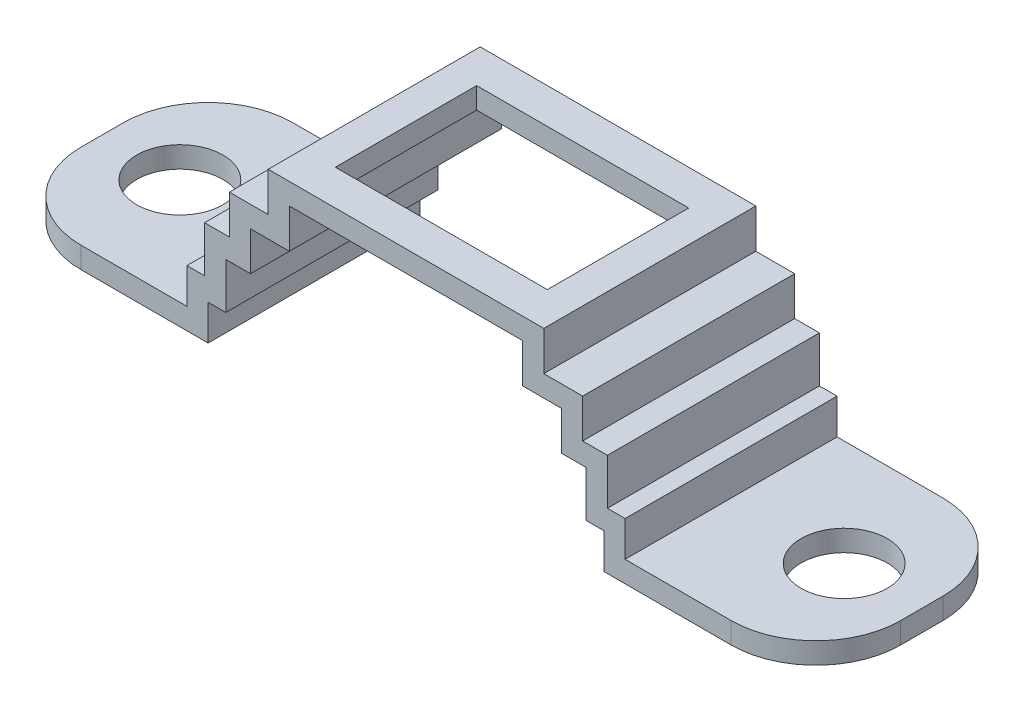
SolidWorks part; units mm, degrees
material "PBT General Purpose"
ref_plane "Front Plane" through (0, 0, 0) normal (0, 0, 1) x (1, 0, 0)
ref_plane "Top Plane" through (0, 0, 0) normal (0, 1, 0) x (1, 0, 0)
ref_plane "Right Plane" through (0, 0, 0) normal (1, 0, 0) x (0, 0, -1)
sketch "Sketch1" plane through (0, 0, 0) normal (0, 0, 1) x (1, 0, 0)
  line L0 (-58, 4.5) -> (-28, 4.5)
  line L1 (-28, 4.5) -> (-28, 9.5)
  line L2 (-28, 9.5) -> (-25.5, 9.5)
  line L3 (-25.5, 9.5) -> (-25.5, 16)
  line L4 (-25.5, 16) -> (-22, 16)
  line L5 (-22, 16) -> (-22, 21.5)
  line L6 (-22, 21.5) -> (-16.5, 21.5)
  line L7 (-16.5, 21.5) -> (-16.5, 27.05)
  line L8 (-16.5, 27.05) -> (0, 27.05)
  circle A0 centre (0, 0) radius 27.05
  dimension "D1" = 54.1
  dimension "D2" = 30
  dimension "D3" = 4.5
  dimension "D4" = 28
  dimension "D5" = 5
  dimension "D6" = 2.5
  dimension "D7" = 6.5
  dimension "D8" = 3.5
  dimension "D9" = 5.5
  dimension "D10" = 5.5
  dimension "D11" = 16.5
  dimension "D12" = 5.55
extrude "Extrude-Thin1" add sketch "Sketch1" along normal mid plane 30 thin contours L0 L1 L2 L3 L4 L5 L6 L7 L8 thin type one direction reverse wall 3
sketch "Sketch2" plane through (0, 7.5, 0) normal (0, 1, 0) x (1, 0, 0)
  line L0 (0, -15) -> (0, 15) construction
  circle A0 centre (-47, 0) radius 6.1
  dimension "D1" = 12.2
  dimension "D2" = 47
extrude "Cut-Extrude1" cut sketch "Sketch2" against normal through all
fillet "Fillet1" radius 12 2 edges at (-58, 6, -15) (-58, 6, 15)
mirror "Mirror1" about plane through (0, 30.05, 15) normal (1, 0, 0) of "Fillet1", "Cut-Extrude1", "Extrude-Thin1"
sketch "Sketch3" plane through (0, 30.05, 0) normal (0, 1, 0) x (1, 0, 0)
  line L1 (15, -10) -> (-15, -10)
  line L2 (15, -10) -> (15, 10)
  line L3 (15, 10) -> (-15, 10)
  line L4 (-15, -10) -> (-15, 10)
  line L5 (15, -10) -> (-15, 10) construction
  line L6 (15, 10) -> (-15, -10) construction
  point P0 (0, 0)
  dimension "D1" = 30
  dimension "D2" = 20
extrude "Cut-Extrude2" cut sketch "Sketch3" against normal through all
